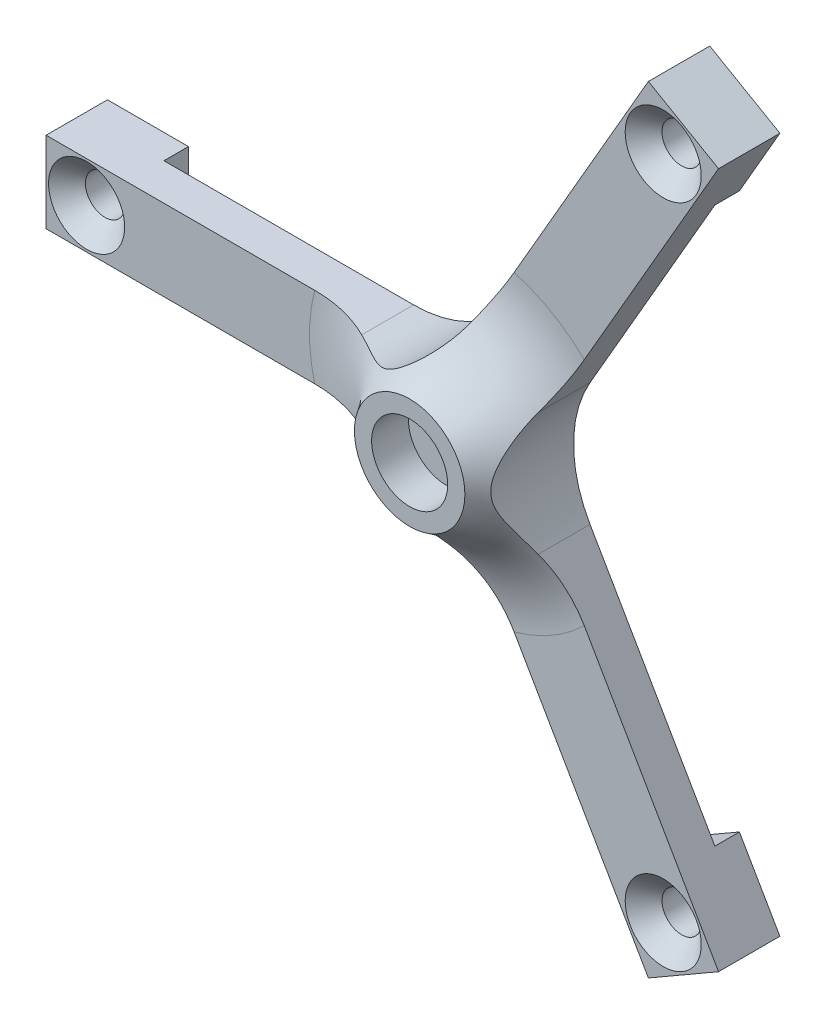
SolidWorks part; units mm, degrees
ref_plane "Plan de face" through (0, 0, 0) normal (0, 0, 1) x (1, 0, 0)
ref_plane "Plan de dessus" through (0, 0, 0) normal (0, 1, 0) x (1, 0, 0)
ref_plane "Plan de droite" through (0, 0, 0) normal (1, 0, 0) x (0, 0, -1)
sketch "Esquisse1" plane through (0, 0, 0) normal (0, 0, 1) x (1, 0, 0)
  line L0 (-34.6246, -3.3) -> (-34.6246, 3.3)
  line L1 (0, -3.5) -> (-34.8246, -3.5) construction
  line L2 (0, -3.5) -> (0, 3.5) construction
  line L3 (0, 3.5) -> (-34.8246, 3.5) construction
  line L4 (-34.8246, -3.5) -> (-34.8246, 3.5) construction
  line L5 (0, -3.5) -> (-34.8246, 3.5) construction
  line L6 (0, 3.5) -> (-34.8246, -3.5) construction
  line L9 (-7.6788, -3.3) -> (-34.6246, -3.3)
  line L10 (14.4544, 31.6357) -> (20.1702, 28.3357)
  line L11 (6.6973, 5) -> (20.1702, 28.3357)
  line L13 (0.9815, 8.3) -> (14.4544, 31.6357)
  line L14 (20.1702, -28.3357) -> (14.4544, -31.6357)
  line L15 (0.9815, -8.3) -> (14.4544, -31.6357)
  line L17 (6.6973, -5) -> (20.1702, -28.3357)
  line L18 (-7.6788, 3.3) -> (-34.6246, 3.3)
  line L19 (-0.2, 3.3) -> (-34.6246, 3.3) construction
  line L20 (-0.2, -3.3) -> (-0.2, 3.3) construction
  line L21 (-0.2, -3.3) -> (-34.6246, -3.3) construction
  circle A0 centre (0, 0) radius 35 construction
  arc A4 (-7.6788, -3.3) -> (0.9815, -8.3) centre (-7.6788, -13.3) cw
  arc A5 (6.6973, -5) -> (6.6973, 5) centre (15.3575, 0) cw
  arc A6 (-7.6788, 3.3) -> (0.9815, 8.3) centre (-7.6788, 13.3) ccw
  point P3 (-17.4123, 0)
  point P28 (0, 0)
  dimension "D1" = 70
  dimension "D7" = 10
  dimension "D2" = 7
  dimension "D5" = 0.2
  dimension "D6" = 3
extrude "Boss.-Extru.1" add sketch "Esquisse1" along normal blind 3
sketch "Esquisse2" plane through (0, 0, 0) normal (0, 0, -1) x (-1, 0, 0)
  line L5 (34.6246, -3.3) -> (7.6788, -3.3) construction
  line L6 (34.6246, 3.3) -> (28.0246, 3.3)
  line L14 (34.6246, 3.3) -> (34.6246, -3.3)
  line L15 (34.6246, -3.3) -> (28.0246, -3.3)
  line L16 (28.0246, 3.3) -> (28.0246, -3.3)
  line L17 (-14.4544, -31.6357) -> (-20.1702, -28.3357)
  line L18 (-14.4544, -31.6357) -> (-11.1544, -25.92)
  line L19 (-11.1544, -25.92) -> (-16.8702, -22.62)
  line L20 (-20.1702, -28.3357) -> (-16.8702, -22.62)
  line L21 (-20.1702, 28.3357) -> (-14.4544, 31.6357)
  line L22 (-20.1702, 28.3357) -> (-16.8702, 22.62)
  line L23 (-16.8702, 22.62) -> (-11.1544, 25.92)
  line L24 (-14.4544, 31.6357) -> (-11.1544, 25.92)
  point P20 (0, 0)
  dimension "D1" = 3
extrude "Boss.-Extru.2" add sketch "Esquisse2" along normal blind 2
sketch "Esquisse3" plane through (0, 0, 3) normal (0, 0, 1) x (1, 0, 0)
  line L0 (-34.6246, 3.3) -> (-34.6246, -3.3) construction
  circle A0 centre (-31.3246, 0) radius 1.6
  circle A1 centre (15.6623, 27.1279) radius 1.6
  circle A2 centre (15.6623, -27.1279) radius 1.6
  point P10 (0, 0)
  dimension "D2" = 3.2
  dimension "D1" = 3.3
  dimension "D3" = 3
extrude "Enlèv. mat.-Extru.1" cut sketch "Esquisse3" against normal through all
sketch "Esquisse4" plane through (0, 0, 3) normal (0, 0, 1) x (1, 0, 0)
  circle A1 centre (0, 0) radius 4.5
  dimension "D1" = 9
extrude "Boss.-Extru.3" add sketch "Esquisse4" along normal blind 5
sketch "Esquisse5" plane through (0, 0, 8) normal (0, 0, 1) x (1, 0, 0)
  circle A0 centre (0, 0) radius 3.1
  dimension "D1" = 6.2
extrude "Enlèv. mat.-Extru.2" cut sketch "Esquisse5" against normal blind 3
chamfer "Chanfrein1" distance 1.5 angle 45 3 edges at (17.2623, 27.1279, 3) (17.2623, -27.1279, 3) (-29.7246, 0, 3)
fillet "Congé1" radius 10 1 edges at (-4.5, 0, 3)
